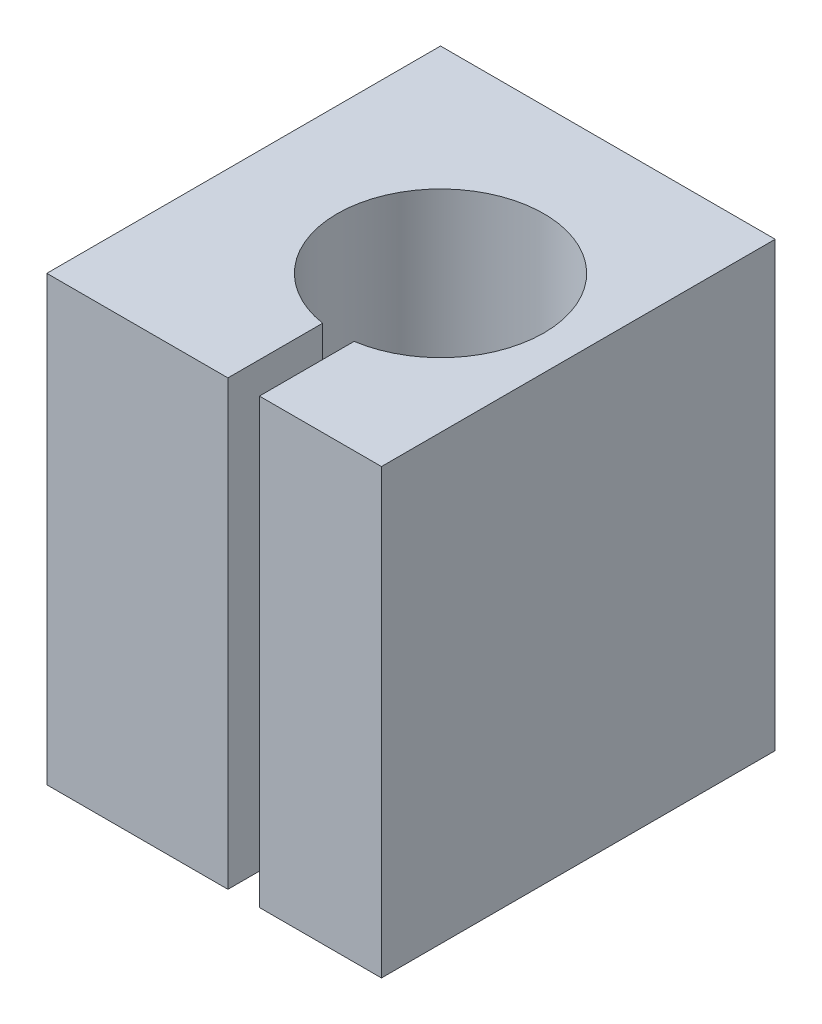
SolidWorks part; units mm, degrees
ref_plane "Спереди" through (0, 0, 0) normal (0, 0, 1) x (1, 0, 0)
ref_plane "Сверху" through (0, 0, 0) normal (0, 1, 0) x (1, 0, 0)
ref_plane "Справа" through (0, 0, 0) normal (1, 0, 0) x (0, 0, -1)
sketch "Эскиз1" plane through (0, 0, 0) normal (0, 1, 0) x (1, 0, 0)
  line L0 (3, 37.5409) -> (3, -34.4773) construction
  line L1 (-17, 20) -> (17, 20)
  line L2 (-17, 20) -> (-17, -20)
  line L3 (-17, -20) -> (1.4, -20)
  line L4 (17, 20) -> (17, -20)
  line L5 (-17, 20) -> (17, -20) construction
  line L6 (-17, -20) -> (17, 20) construction
  line L7 (-42.3455, 0) -> (34.4636, 0) construction
  line L8 (1.4, -20) -> (1.4, -10.3774)
  line L9 (4.6, -20) -> (4.6, -10.3774)
  line L10 (4.6, -20) -> (17, -20)
  arc A0 (4.6, -10.3774) -> (1.4, -10.3774) centre (3, 0) ccw
  point P0 (0, 0)
  dimension "D5" = 21
  dimension "D1" = 34
  dimension "D2" = 40
  dimension "D3" = 14
  dimension "D4" = 20
  dimension "D6" = 1.6
  dimension "D7" = 1.6
extrude "Бобышка-Вытянуть1" add sketch "Эскиз1" along normal blind 45
